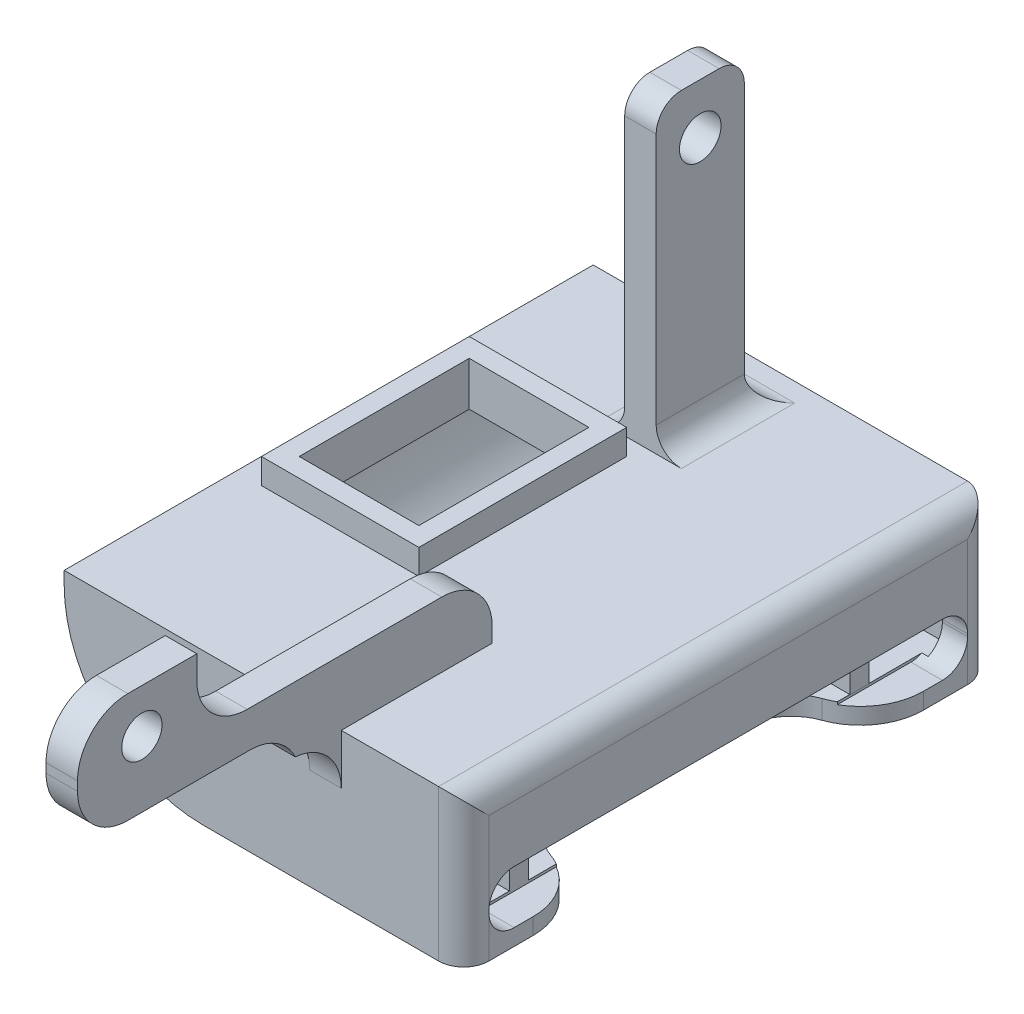
SolidWorks part; units mm, degrees
ref_plane "Alzado" through (0, 0, 0) normal (0, 0, 1) x (1, 0, 0)
ref_plane "Planta" through (0, 0, 0) normal (0, 1, 0) x (1, 0, 0)
ref_plane "Vista lateral" through (0, 0, 0) normal (1, 0, 0) x (0, 0, -1)
sketch "Croquis1" plane through (0, 0, 0) normal (0, 1, 0) x (1, 0, 0)
  line L0 (30.6835, -17.7215) -> (30.6835, -21.7215)
  line L1 (-29.3165, 14.2785) -> (30.6835, 14.2785)
  line L2 (-29.3165, 14.2785) -> (-29.3165, -21.7215)
  line L3 (-29.3165, -21.7215) -> (30.6835, -21.7215)
  line L4 (30.6835, 14.2785) -> (30.6835, 10.2785)
  line L5 (30.6835, 10.2785) -> (2.6835, 10.2785)
  line L7 (30.6835, -17.7215) -> (2.6835, -17.7215)
  line L8 (2.6835, 10.2785) -> (2.6835, -17.7215)
  dimension "D1" = 60
  dimension "D2" = 36
  dimension "D3" = 28
  dimension "D4" = 4
  dimension "D5" = 28
extrude "Saliente-Extruir1" add sketch "Croquis1" along normal blind 12
sketch "Croquis2" plane through (0, 12, 0) normal (0, 1, 0) x (1, 0, 0)
  line L0 (-29.3165, -21.7215) -> (30.6835, -21.7215) construction
  line L1 (-25.8165, 3.9385) -> (-16.3165, 3.9385)
  line L2 (-16.3165, 3.9385) -> (-16.3165, -9.5615)
  line L3 (-25.8165, -9.5615) -> (-16.3165, -9.5615)
  line L4 (-25.8165, 3.9385) -> (-25.8165, -9.5615)
  line L5 (2.6835, 5.4385) -> (-27.3165, 5.4385) construction
  line L6 (2.6835, -17.7215) -> (2.6835, 10.2785) construction
  line L8 (-27.3165, 5.4385) -> (-14.8165, 5.4385)
  line L9 (-27.3165, 5.4385) -> (-27.3165, -11.0615)
  line L10 (-27.3165, -11.0615) -> (-14.8165, -11.0615)
  line L11 (-14.8165, 5.4385) -> (-14.8165, -11.0615)
  dimension "D1" = 1.5
  dimension "D2" = 12.5
  dimension "D3" = 16.5
  dimension "D4" = 10.66
extrude "Saliente-Extruir2" add sketch "Croquis2" along normal blind 2
sketch "Croquis3" plane through (0, 12, 0) normal (0, 1, 0) x (1, 0, 0)
  line L0 (-7.8165, -12.7415) -> (-7.8165, -41.5605)
  line L1 (-9.8165, -12.7415) -> (-7.8165, -12.7415)
  line L2 (-29.3165, 14.2785) -> (-29.3165, -21.7215) construction
  line L3 (-9.8165, -12.7415) -> (-9.8165, -41.5605)
  line L4 (30.6835, 14.2785) -> (-29.3165, 14.2785) construction
  line L7 (-9.8165, -41.5605) -> (-9.8165, -45.6642)
  line L8 (-9.8165, -45.6642) -> (-7.8165, -45.6642)
  line L9 (-7.8165, -41.5605) -> (-7.8165, -45.6642)
  dimension "D1" = 19.5
  dimension "D2" = 27.02
extrude "Saliente-Extruir4" add sketch "Croquis3" along normal blind 11
sketch "Croquis4" plane through (-9.8165, 0, 0) normal (-1, 0, 0) x (0, 0, 1)
  line L0 (-5.4385, 12) -> (40.5515, 12) construction
  line L1 (21.7215, 12) -> (45.6642, 12) construction
  line L2 (40.5515, 12) -> (40.5515, 19.5075) construction
  line L3 (12.7415, 23) -> (12.7415, 12) construction
  circle A0 centre (40.5515, 19.5075) radius 1.6
  dimension "D1" = 27.81
extrude "Cortar-Extruir1" cut sketch "Croquis4" against normal blind 2.5
sketch "Croquis5" plane through (-9.8165, 0, 0) normal (-1, 0, 0) x (0, 0, 1)
  line L0 (28.3713, 14.2761) -> (28.3713, 12)
  line L1 (12.7415, 23) -> (36.1915, 23)
  line L2 (12.7415, 23) -> (12.7415, 17.1784)
  line L3 (12.7415, 17.1784) -> (36.1915, 17.1784)
  line L4 (36.1915, 23) -> (36.1915, 17.1784)
  line L5 (45.6642, 12) -> (28.3713, 12)
  line L6 (45.6642, 12) -> (45.6642, 14.2761)
  line L7 (45.6642, 14.2761) -> (28.3713, 14.2761)
extrude "Cortar-Extruir2" cut sketch "Croquis5" against normal blind 2
sketch "Croquis6" plane through (0, 0, 21.7215) normal (0, 0, 1) x (1, 0, 0)
  line L6 (-29.3165, 0) -> (30.6835, 0)
  line L7 (30.6835, 0) -> (30.6835, 12)
  line L8 (30.6835, 12) -> (-7.8165, 12)
  line L9 (-7.8165, 12) -> (-9.8165, 12)
  line L10 (-9.8165, 12) -> (-29.3165, 12)
  line L11 (-29.3165, 12) -> (-29.3165, 0)
  line L12 (-29.3165, 0) -> (30.6835, 0)
  line L13 (30.6835, 0) -> (30.6835, 12)
  line L14 (30.6835, 12) -> (-7.8165, 12)
  line L15 (-7.8165, 12) -> (-9.8165, 12)
  line L16 (-9.8165, 12) -> (-29.3165, 12)
  line L17 (-29.3165, 12) -> (-29.3165, 0)
  dimension "D1" = 0
extrude "Saliente-Extruir5" add sketch "Croquis6" along normal blind 3
sketch "Croquis7" plane through (0, 0, -14.2785) normal (0, 0, -1) x (-1, 0, 0)
  line L4 (-30.6835, 0) -> (29.3165, 0)
  line L5 (29.3165, 0) -> (29.3165, 12)
  line L6 (29.3165, 12) -> (-30.6835, 12)
  line L7 (-30.6835, 12) -> (-30.6835, 0)
  line L8 (-30.6835, 0) -> (29.3165, 0)
  line L9 (29.3165, 0) -> (29.3165, 12)
  line L10 (29.3165, 12) -> (-30.6835, 12)
  line L11 (-30.6835, 12) -> (-30.6835, 0)
  dimension "D1" = 0
extrude "Saliente-Extruir6" add sketch "Croquis7" along normal blind 3
sketch "Croquis8" plane through (0, 0, 24.7215) normal (0, 0, 1) x (1, 0, 0)
  line L2 (-18.3165, 0) -> (-29.3165, 0)
  line L4 (-29.3165, 0) -> (-29.3165, 11)
  line L5 (-15.3452, 0) -> (-15.2756, 0)
  arc A0 (-18.3165, 0) -> (-29.3165, 11) centre (-18.3165, 11) cw
  line M1 (-29.3165, 12) -> (-29.3165, 0)
  line M2 (-29.3165, 0) -> (30.6835, 0)
  dimension "D1" = 11
extrude "Cortar-Extruir3" cut sketch "Croquis8" against normal blind 42 contours A0 M2 M1 region at (-26.8594, 2.457, 24.7215)
shell "Vaciado4" thickness 1.5 removed face at (-21.0665, 12, 2.8115)
fillet "Redondeo2" radius 4 4 edges at (-8.8165, 12, 24.7215) (-8.8165, 14.2761, 28.3713) (-8.8165, 17.1784, 36.1915) (-8.8165, 17.1784, 12.7415)
fillet "Redondeo3" radius 4 2 edges at (-8.8165, 23, 45.6642) (-8.8165, 14.2761, 45.6642)
sketch "Croquis10" plane through (0, 12, 0) normal (0, 1, 0) x (1, 0, 0)
  line L0 (-29.3165, 17.2785) -> (-29.3165, -24.7215) construction
  line L1 (-13.8165, 13.7785) -> (-16.3165, 13.7785)
  line L2 (-13.8165, 13.7785) -> (-13.8165, 6.7785)
  line L3 (-13.8165, 6.7785) -> (-16.3165, 6.7785)
  line L4 (-16.3165, 13.7785) -> (-16.3165, 6.7785)
  line L5 (-29.3165, 17.2785) -> (30.6835, 17.2785) construction
  dimension "D1" = 7
  dimension "D2" = 2.5
  dimension "D3" = 13
  dimension "D4" = 3.5
extrude "Saliente-Extruir8" add sketch "Croquis10" along normal blind 24
sketch "Croquis11" plane through (-16.3165, 0, 0) normal (-1, 0, 0) x (0, 0, 1)
  line L0 (-10.2785, 36) -> (-10.2785, 12) construction
  line L1 (-13.7785, 36) -> (-6.7785, 36) construction
  line L2 (-13.7785, 12) -> (-6.7785, 12) construction
  line L3 (-10.2785, 12) -> (-10.2785, 32.0033) construction
  circle A0 centre (-10.2785, 32.0033) radius 1.65
extrude "Cortar-Extruir4" cut sketch "Croquis11" against normal blind 2.5
sketch "Croquis14" plane through (-7.8165, 0, 0) normal (1, 0, 0) x (0, 0, -1)
  line L8 (-36.1915, 23) -> (-41.6642, 23)
  line L9 (-45.6642, 19) -> (-45.6642, 18.2761)
  line L10 (-41.6642, 14.2761) -> (-31.9808, 14.2761)
  line L11 (-24.7215, 8.0154) -> (-24.7215, 12)
  line L12 (-24.7215, 12) -> (-12.7415, 12)
  line L13 (-12.7415, 12) -> (-12.7415, 13.1784)
  line L14 (-16.7415, 17.1784) -> (-32.1915, 17.1784)
  line L15 (-36.1915, 21.1784) -> (-36.1915, 23)
  line L16 (-36.1915, 23) -> (-41.6642, 23)
  line L17 (-45.6642, 19) -> (-45.6642, 18.2761)
  line L18 (-41.6642, 14.2761) -> (-31.9808, 14.2761)
  line L19 (-24.7215, 8.0154) -> (-24.7215, 12)
  line L20 (-24.7215, 12) -> (-12.7415, 12)
  line L21 (-12.7415, 12) -> (-12.7415, 13.1784)
  line L22 (-16.7415, 17.1784) -> (-32.1915, 17.1784)
  line L23 (-36.1915, 21.1784) -> (-36.1915, 23)
  circle A0 centre (-40.5515, 19.5075) radius 1.6 construction
  circle A1 centre (-40.5515, 19.5075) radius 1.6
  arc A7 (-41.6642, 23) -> (-45.6642, 19) centre (-41.6642, 19) ccw
  arc A8 (-45.6642, 18.2761) -> (-41.6642, 14.2761) centre (-41.6642, 18.2761) ccw
  arc A9 (-28.3713, 12) -> (-31.9808, 14.2761) centre (-31.9808, 10.2761) ccw
  arc A10 (-24.7215, 8.0154) -> (-28.3713, 12) centre (-28.7215, 8.0154) ccw
  arc A12 (-12.7415, 13.1784) -> (-16.7415, 17.1784) centre (-16.7415, 13.1784) ccw
  arc A13 (-36.1915, 21.1784) -> (-32.1915, 17.1784) centre (-32.1915, 21.1784) ccw
  arc A14 (-41.6642, 23) -> (-45.6642, 19) centre (-41.6642, 19) ccw
  arc A15 (-45.6642, 18.2761) -> (-41.6642, 14.2761) centre (-41.6642, 18.2761) ccw
  arc A16 (-28.3713, 12) -> (-31.9808, 14.2761) centre (-31.9808, 10.2761) ccw
  arc A17 (-24.7215, 8.0154) -> (-28.3713, 12) centre (-28.7215, 8.0154) ccw
  arc A19 (-12.7415, 13.1784) -> (-16.7415, 17.1784) centre (-16.7415, 13.1784) ccw
  arc A20 (-36.1915, 21.1784) -> (-32.1915, 17.1784) centre (-32.1915, 21.1784) ccw
  dimension "D1" = 0
extrude "Saliente-Extruir10" add sketch "Croquis14" along normal blind 0.5
sketch "Croquis15" plane through (0, 12, 0) normal (0, 1, 0) x (1, 0, 0)
  line L0 (30.6835, -24.7215) -> (-7.3165, -24.7215) construction
  line L1 (2.4073, -24.7215) -> (30.6835, -24.7215)
  line L2 (2.4073, -24.7215) -> (2.4073, 17.2785)
  line L3 (2.4073, 17.2785) -> (30.6835, 17.2785)
  line L4 (30.6835, -24.7215) -> (30.6835, 17.2785)
extrude "Cortar-Extruir5" cut sketch "Croquis15" against normal blind 12
sketch "Croquis16" plane through (2.4073, 0, 0) normal (1, 0, 0) x (0, 0, -1)
  line L1 (-24.7215, 12) -> (17.2785, 12)
  line L2 (-24.7215, 12) -> (-24.7215, 0)
  line L3 (-24.7215, 0) -> (17.2785, 0)
  line L4 (17.2785, 12) -> (17.2785, 0)
extrude "Saliente-Extruir11" add sketch "Croquis16" against normal blind 2
sketch "Croquis18" plane through (2.4073, 0, 0) normal (1, 0, 0) x (0, 0, -1)
  line L0 (-24.7215, 6) -> (17.2785, 6) construction
  line L1 (-24.7215, 0) -> (-24.7215, 12) construction
  line L2 (17.2785, 0) -> (17.2785, 12) construction
  line L3 (17.2785, 6) -> (-3.7215, 6) construction
  line L4 (-3.7215, 6) -> (-3.7215, 0) construction
  line L5 (17.2785, 0) -> (-24.7215, 0) construction
  line L6 (-3.7215, 0) -> (-3.7215, 12) construction
  line L7 (17.2785, 12) -> (-24.7215, 12) construction
  line L9 (-20.7215, 5.5) -> (13.2785, 5.5)
  line L10 (-22.7215, 3.5) -> (-22.7215, 3.3)
  line L11 (-20.7215, 1.3) -> (13.2785, 1.3)
  line L12 (15.2785, 3.5) -> (15.2785, 3.3)
  arc A0 (15.2785, 3.5) -> (13.2785, 5.5) centre (13.2785, 3.5) ccw
  arc A1 (15.2785, 3.3) -> (13.2785, 1.3) centre (13.2785, 3.3) cw
  arc A2 (-22.7215, 3.3) -> (-20.7215, 1.3) centre (-20.7215, 3.3) ccw
  arc A3 (-22.7215, 3.5) -> (-20.7215, 5.5) centre (-20.7215, 3.5) cw
  point P19 (15.2785, 5.5)
  point P22 (15.2785, 1.3)
  point P27 (-22.7215, 5.5)
  dimension "D6" = 2
  dimension "D1" = 38
  dimension "D2" = 4.2
  dimension "D3" = 2
  dimension "D4" = 2
  dimension "D5" = 6.5
extrude "Cortar-Extruir6" cut sketch "Croquis18" against normal blind 2.5
sketch "Croquis19" plane through (0, 1.5, 0) normal (0, 1, 0) x (1, 0, 0)
  line L0 (-18.3165, 15.7785) -> (-18.3165, -23.2215) construction
  line L1 (-18.3165, -18.5961) -> (-0.0927, -18.5961)
  line L2 (-18.3165, -18.5961) -> (-18.3165, -17.0961)
  line L3 (-18.3165, -17.0961) -> (-0.0927, -17.0961)
  line L4 (-0.0927, -18.5961) -> (-0.0927, -17.0961)
  line L5 (-0.0927, -21.5933) -> (-0.0927, 14.1503) construction
  line L6 (-18.3361, -5.3453) -> (-0.1124, -5.3453)
  line L7 (-18.3361, -5.3453) -> (-18.3361, -3.8453)
  line L8 (-18.3361, -3.8453) -> (-0.1124, -3.8453)
  line L9 (-0.1124, -5.3453) -> (-0.1124, -3.8453)
  line L10 (-18.2876, 8.4292) -> (-0.0638, 8.4292)
  line L11 (-18.2876, 8.4292) -> (-18.2876, 9.9292)
  line L12 (-18.2876, 9.9292) -> (-0.0638, 9.9292)
  line L13 (-0.0638, 8.4292) -> (-0.0638, 9.9292)
  dimension "D1" = 1.5
extrude "Saliente-Extruir16" add sketch "Croquis19" along normal up to surface (9 mm away)
fillet "Redondeo4" radius 2 3 edges at (2.4073, 6, 24.7215) (2.4073, 6, -17.2785) (2.4073, 12, 3.7215)
fillet "Redondeo5" radius 2 2 edges at (-15.0665, 36, -6.7785) (-15.0665, 36, -13.7785)
fillet "Redondeo6" radius 2 3 edges at (-16.3165, 12, -10.2785) (-15.0665, 12, -13.7785) (-13.8165, 12, -10.2785)
sketch "Croquis20" plane through (0, 0, 0) normal (0, -1, 0) x (1, 0, 0)
  line L0 (2.4073, -15.2785) -> (2.4073, 22.7215) construction
  line L1 (2.4073, 14.7215) -> (0.4073, 14.7215)
  line L2 (2.4073, 14.7215) -> (2.4073, -7.2785)
  line L3 (2.4073, -7.2785) -> (0.4073, -7.2785)
  line L4 (-3.5927, 10.7215) -> (-3.5927, -3.2785)
  line L5 (-18.3165, 24.7215) -> (0.4073, 24.7215) construction
  line L6 (0.4073, -17.2785) -> (-18.3165, -17.2785) construction
  arc A0 (-3.5927, -3.2785) -> (0.4073, -7.2785) centre (0.4073, -3.2785) ccw
  arc A1 (0.4073, 14.7215) -> (-3.5927, 10.7215) centre (0.4073, 10.7215) ccw
  point P14 (-3.5927, 14.7215)
  dimension "D5" = 4
  dimension "D1" = 22
  dimension "D2" = 10
  dimension "D3" = 10
  dimension "D4" = 6
extrude "Cortar-Extruir7" cut sketch "Croquis20" against normal blind 2
fillet "Redondeo7" radius 5 2 edges at (2.4073, 0.65, -7.2785) (2.4073, 0.65, 14.7215)
fillet "Redondeo8" radius 5 1 edges at (-0.1124, 2, 4.5953)
